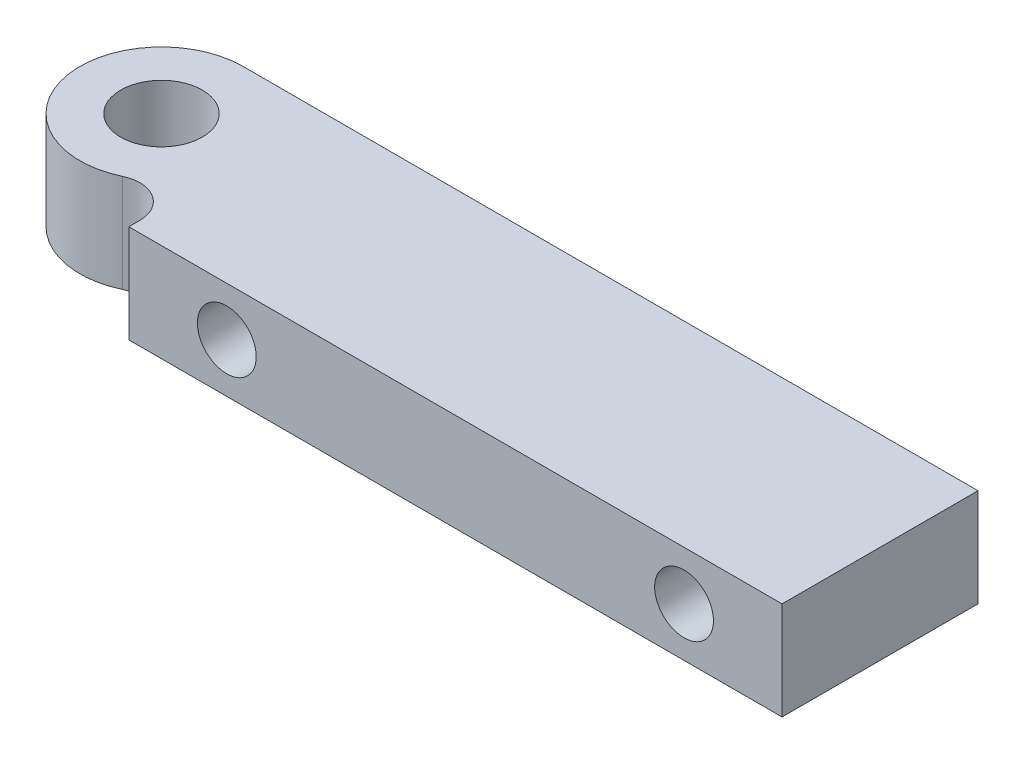
SolidWorks part; units mm, degrees
ref_plane "Front Plane" through (0, 0, 0) normal (0, 0, 1) x (1, 0, 0)
ref_plane "Top Plane" through (0, 0, 0) normal (0, 1, 0) x (1, 0, 0)
ref_plane "Right Plane" through (0, 0, 0) normal (1, 0, 0) x (0, 0, -1)
sketch "Sketch1" plane through (0, 0, 0) normal (0, 1, 0) x (1, 0, 0)
  line L0 (0, 6.35) -> (12.3665, 6.35)
  line L1 (12.3665, 6.35) -> (57.15, 6.35)
  line L2 (6.35, 0) -> (6.35, -8.89)
  line L3 (6.35, -8.89) -> (57.15, -8.89)
  line L4 (57.15, 6.35) -> (57.15, -8.89)
  circle A0 centre (0, 0) radius 3.175
  arc A1 (0, 6.35) -> (6.35, 0) centre (0, 0) ccw
  dimension "D1" = 12.7
  dimension "D2" = 6.35
  dimension "D3" = 6.35
  dimension "D4" = 50.8
  dimension "D5" = 15.24
extrude "Boss-Extrude1" add sketch "Sketch1" along normal mid plane 7.62
fillet "Fillet1" radius 2.54 1 edges at (6.35, 0, 0)
sketch "Sketch2" plane through (0, 0, 8.89) normal (0, 0, 1) x (1, 0, 0)
  circle A0 centre (49.53, 0) radius 1.8987 construction
  circle A1 centre (13.97, 0) radius 1.8987 construction
  circle A2 centre (49.53, 0) radius 1.8986
  circle A3 centre (13.97, 0) radius 1.8986
  circle A4 centre (13.97, 0) radius 2.286
  circle A5 centre (49.53, 0) radius 2.286
  dimension "D1" = 4.572
  dimension "D2" = 4.572
extrude "Cut-Extrude1" cut sketch "Sketch2" against normal blind 5.08 contours A4 | A5 | A3 | A2 region at (49.53, 0, 8.89) region at (13.97, 0, 8.89) region at (11.7487, 0, 8.89) region at (47.3087, 0, 8.89)
